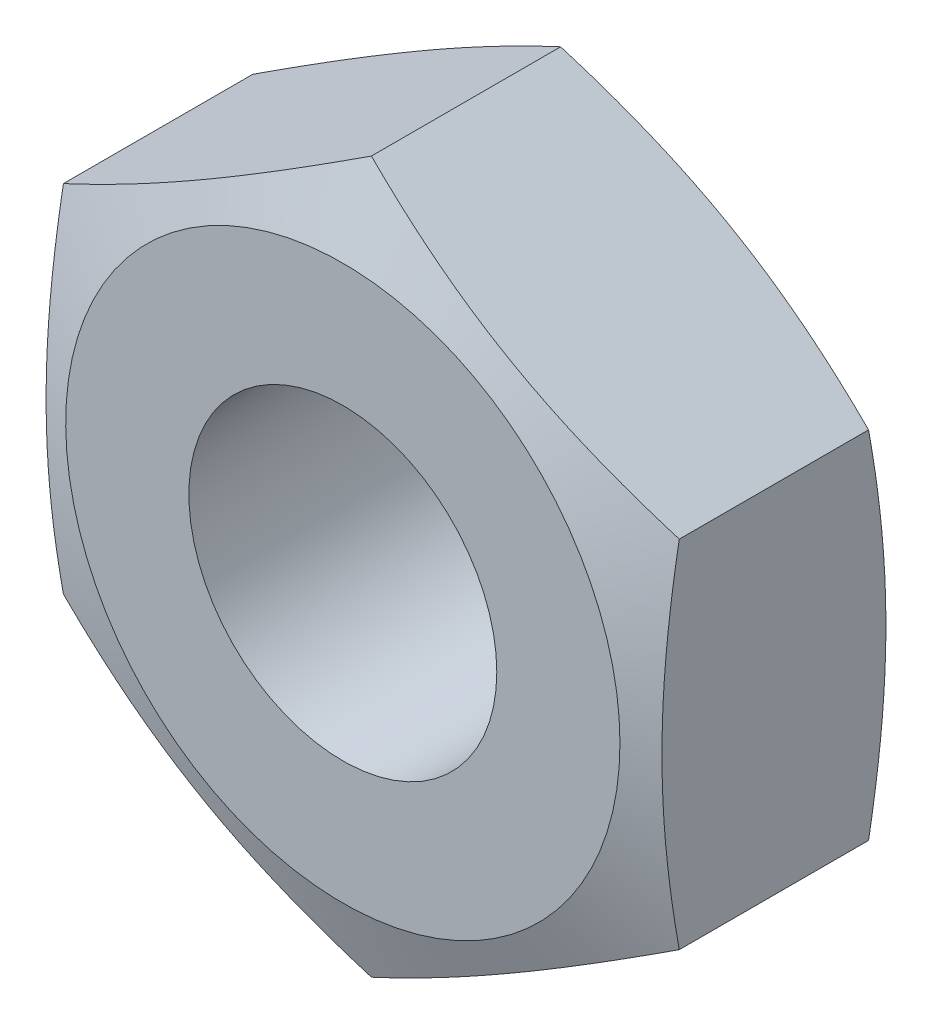
SolidWorks part; units mm, degrees
ref_plane "前视基准面" through (0, 0, 0) normal (0, 0, 1) x (1, 0, 0)
ref_plane "上视基准面" through (0, 0, 0) normal (0, 1, 0) x (1, 0, 0)
ref_plane "右视基准面" through (0, 0, 0) normal (1, 0, 0) x (0, 0, -1)
sketch "草图1" plane through (0, 0, 0) normal (0, 0, 1) x (1, 0, 0)
  line L1 (0, 2.3094) -> (-2, 1.1547)
  line L2 (-2, 1.1547) -> (-2, -1.1547)
  line L3 (-2, -1.1547) -> (0, -2.3094)
  line L4 (0, -2.3094) -> (2, -1.1547)
  line L5 (2, -1.1547) -> (2, 1.1547)
  line L6 (2, 1.1547) -> (0, 2.3094)
  circle A0 centre (0, 0) radius 2 construction
  dimension "s" = 4
extrude "凸台-拉伸1" add sketch "草图1" along normal blind 1.6
sketch "草图4" plane through (0, 0, 0) normal (1, 0, 0) x (0, 0, -1)
  line L0 (-1.6, -1.8) -> (-1.4146, -2.3094)
  line L1 (-1.6, -1.1547) -> (-1.6, -2.3094) construction
  line L2 (-1.6, -2.3094) -> (0, -2.3094) construction
  line L3 (-1.4146, -2.3094) -> (-1.6, -2.3094)
  line L4 (-1.6, -2.3094) -> (-1.6, -1.8)
  line L5 (-1.6, 0) -> (0, 0) construction
  line L6 (-1.6, 1.1547) -> (-1.6, -1.1547) construction
  line L7 (0, 1.1547) -> (0, -1.1547) construction
  dimension "D1" = 20
  dimension "D2" = 1.8
revolve "切除-旋转1" cut sketch "草图4" angle 360 about L5
ref_plane "基准面1" through (0, 0, 0.8) normal (0, 0, 1) x (1, 0, 0)
mirror "镜向1" about plane through (0, 0, 0.8) normal (0, 0, 1) of "切除-旋转1"
sketch "草图5" plane through (0, 0, 1.6) normal (0, 0, 1) x (1, 0, 0)
  circle A0 centre (0, 0) radius 1
  dimension "D1" = 2
extrude "切除-拉伸1" cut sketch "草图5" against normal through all
ref_axis "基准轴1" through (0, 0, 0) along (0, 0, 1)
ref_plane "基准面2" through (0, 0, 0) normal (0, 0, -1) x (-1, 0, 0)
ref_plane "基准面3" through (0, 0, 1.6) normal (0, 0, 1) x (1, 0, 0)
equation "\"D2@草图4\"= \"s@草图1\" * 0.45"
